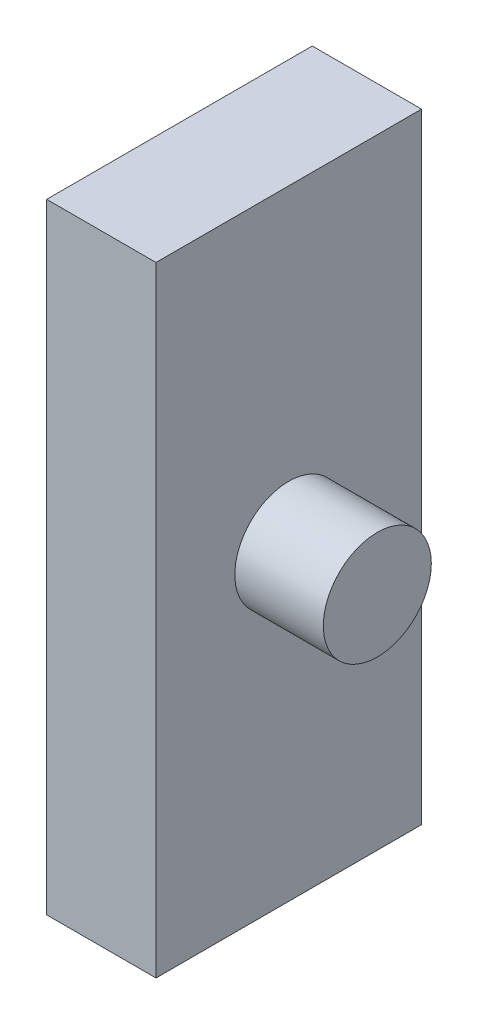
SolidWorks part; units mm, degrees
ref_plane "Front Plane" through (0, 0, 0) normal (0, 0, 1) x (1, 0, 0)
ref_plane "Top Plane" through (0, 0, 0) normal (0, 1, 0) x (1, 0, 0)
ref_plane "Right Plane" through (0, 0, 0) normal (1, 0, 0) x (0, 0, -1)
sketch "Sketch1" plane through (0, 0, 0) normal (1, 0, 0) x (0, 0, -1)
  line L0 (5.9125, 17.5) -> (9.0875, 17.5) construction
  line L1 (5.9125, 24) -> (9.0875, 24)
  line L2 (5.9125, 24) -> (5.9125, 11)
  line L3 (5.9125, 11) -> (9.0875, 11)
  line L4 (9.0875, 24) -> (9.0875, 11)
  line L5 (7.5, 24) -> (7.5, 11) construction
  line L6 (7.5, 35) -> (7.5, 0) construction
  line L15 (0, 35) -> (15, 35)
  line L16 (0, 35) -> (0, 0)
  line L17 (0, 0) -> (15, 0)
  line L18 (15, 35) -> (15, 0)
  line L19 (0, 17.5) -> (15, 17.5) construction
  dimension "D2" = 3.175
  dimension "D3" = 13
  dimension "D4" = 15
  dimension "D5" = 35
extrude "Boss-Extrude1" add sketch "Sketch1" along normal blind 4.175
sketch "Sketch2" plane through (4.175, 0, 0) normal (1, 0, 0) x (0, 0, -1)
  line L1 (0, 35) -> (15, 35)
  line L2 (0, 35) -> (0, 0)
  line L3 (0, 0) -> (15, 0)
  line L4 (15, 35) -> (15, 0)
extrude "Boss-Extrude2" add sketch "Sketch2" along normal blind 2
sketch "Sketch3" plane through (6.175, 0, 0) normal (1, 0, 0) x (0, 0, -1)
  line L0 (7.5, 35) -> (7.5, 0) construction
  line L1 (15, 35) -> (0, 35) construction
  line L2 (0, 0) -> (15, 0) construction
  line L3 (0, 17.5) -> (15, 17.5) construction
  line L4 (0, 35) -> (0, 0) construction
  line L5 (15, 0) -> (15, 35) construction
  circle A0 centre (7.5, 17.5) radius 3.05
  dimension "D1" = 6.1
extrude "Boss-Extrude3" add sketch "Sketch3" along normal blind 5
